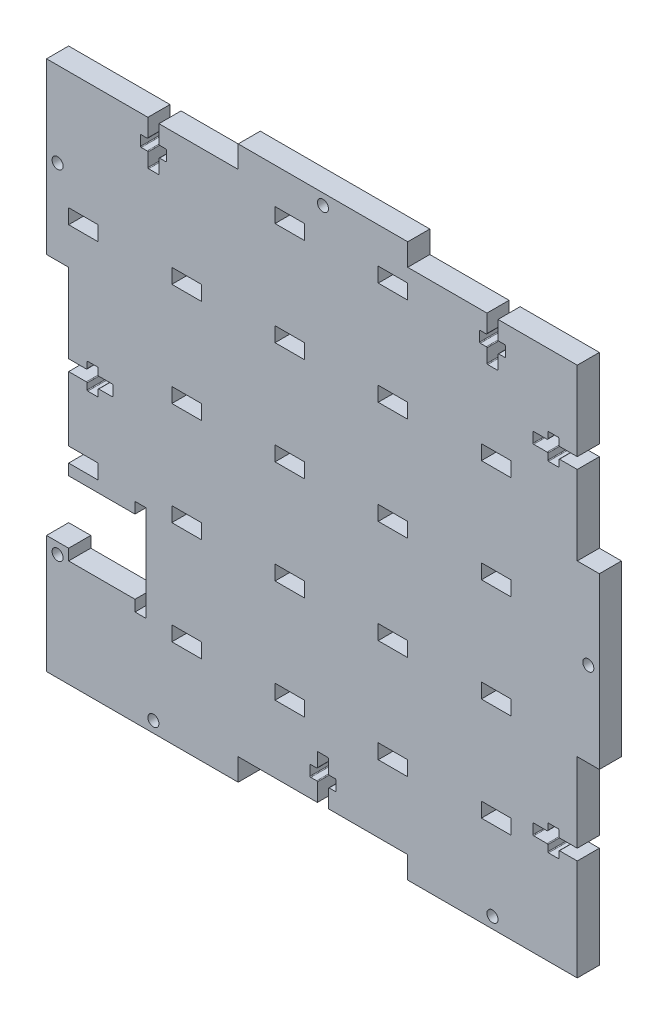
SolidWorks part; units mm, degrees
ref_plane "Front Plane" through (0, 0, 0) normal (0, 0, 1) x (1, 0, 0)
ref_plane "Top Plane" through (0, 0, 0) normal (0, 1, 0) x (1, 0, 0)
ref_plane "Right Plane" through (0, 0, 0) normal (1, 0, 0) x (0, 0, -1)
sketch "Sketch1" plane through (0, 0, 0) normal (0, 0, 1) x (1, 0, 0)
  line L0 (-69, 69) -> (-23, 69)
  line L5 (-75, -75) -> (75, -75) construction
  line L6 (-75, -75) -> (-75, 75) construction
  line L7 (-75, 75) -> (75, 75) construction
  line L8 (75, -75) -> (75, 75) construction
  line L9 (75, 23) -> (69, 23)
  line L10 (69, -23) -> (75, -23)
  line L11 (-69, -69) -> (69, -69) construction
  line L12 (-69, -69) -> (-69, 69) construction
  line L13 (-69, 69) -> (69, 69) construction
  line L14 (69, -69) -> (69, 69) construction
  line L15 (-69, -69) -> (69, 69) construction
  line L16 (69, -69) -> (69, -23)
  line L17 (-23, 69) -> (-23, 75)
  line L18 (-23, 75) -> (23, 75)
  line L19 (23, 75) -> (23, 69)
  line L20 (23, 69) -> (69, 69)
  line L21 (75, -23) -> (75, 23)
  line L22 (69, 23) -> (69, 69)
  line L23 (-75, 23) -> (-69, 23)
  line L24 (-69, 69) -> (-75, 69)
  line L25 (-75, 69) -> (-75, 23)
  line L26 (69, -69) -> (69, -75)
  line L27 (69, -75) -> (23, -75)
  line L28 (23, -75) -> (23, -69)
  line L29 (23, -69) -> (-23, -69)
  line L30 (-23, -69) -> (-23, -75)
  line L31 (-23, -75) -> (-69, -75)
  line L32 (-69, -75) -> (-69, -69) construction
  line L33 (-69, 23) -> (-69, -23)
  line L34 (-69, -23) -> (-75, -23)
  line L35 (-75, -23) -> (-75, -69)
  line L36 (-75, -69) -> (-69, -69) construction
  line L37 (-46, 69) -> (-46, -75) construction
  line L38 (-69, 69) -> (69, -69) construction
  line L39 (-75, -75) -> (-69, -75)
  line L40 (-75, -75) -> (-75, -69)
  point P0 (0, 0)
  point P6 (-7, -7)
  point P26 (0, -75)
  point P27 (-75, 0)
  dimension "D1" = 150
  dimension "D2" = 150
  dimension "D5" = 46
  dimension "D3" = 6
  dimension "D6" = 6
  dimension "D7" = 6
extrude "Box Side" add sketch "Sketch1" along normal blind 6
sketch "Sketch2" plane through (0, 0, 6) normal (0, 0, 1) x (1, 0, 0)
  line L0 (23, 72) -> (-23, 72) construction
  line L1 (23, 75) -> (23, 69) construction
  line L2 (-23, 69) -> (-23, 75) construction
  line L3 (-46, 69) -> (-46, -75) construction
  line L5 (0, 75) -> (0, 69) construction
  line L6 (-23, 75) -> (23, 75) construction
  line L7 (-69, 69) -> (69, 69) construction
  line L16 (-46, 69) -> (-46, -75) construction
  line L21 (0, -69) -> (0, 69) construction
  line L35 (-69, 69) -> (-23, 69) construction
  line L36 (-44.5, 69) -> (-44.5, 64.2)
  line L37 (-44.3, 64) -> (-42.7, 64)
  line L38 (-42.5, 63.8) -> (-42.5, 61.2)
  line L39 (-42.7, 61) -> (-44.3, 61)
  line L40 (-44.5, 60.8) -> (-44.5, 57.2)
  line L46 (-44.7, 57) -> (-47.3, 57)
  line L48 (-44.5, 69) -> (-47.5, 69)
  line L51 (-47.5, 60.8) -> (-47.5, 57.2)
  line L52 (-49.3, 61) -> (-47.7, 61)
  line L53 (-49.5, 63.8) -> (-49.5, 61.2)
  line L54 (-47.7, 64) -> (-49.3, 64)
  line L55 (-47.5, 69) -> (-47.5, 64.2)
  line L56 (47.5, 69) -> (47.5, 64.2)
  line L57 (47.7, 64) -> (49.3, 64)
  line L58 (49.5, 63.8) -> (49.5, 61.2)
  line L59 (49.3, 61) -> (47.7, 61)
  line L60 (47.5, 60.8) -> (47.5, 57.2)
  line L61 (44.5, 69) -> (47.5, 69)
  line L62 (44.7, 57) -> (47.3, 57)
  line L63 (44.5, 60.8) -> (44.5, 57.2)
  line L64 (42.7, 61) -> (44.3, 61)
  line L65 (42.5, 63.8) -> (42.5, 61.2)
  line L66 (44.3, 64) -> (42.7, 64)
  line L67 (44.5, 69) -> (44.5, 64.2)
  line L68 (-69, -69) -> (69, 69) construction
  line L69 (-69, -69) -> (69, 69) construction
  line L70 (75, 0) -> (69, 0) construction
  line L71 (72, 23) -> (72, -23) construction
  line L72 (69, 44.5) -> (64.2, 44.5)
  line L73 (64, 44.3) -> (64, 42.7)
  line L74 (63.8, 42.5) -> (61.2, 42.5)
  line L75 (61, 42.7) -> (61, 44.3)
  line L76 (60.8, 44.5) -> (57.2, 44.5)
  line L77 (57, 44.7) -> (57, 47.3)
  line L78 (69, 44.5) -> (69, 47.5)
  line L79 (60.8, 47.5) -> (57.2, 47.5)
  line L80 (61, 49.3) -> (61, 47.7)
  line L81 (63.8, 49.5) -> (61.2, 49.5)
  line L82 (64, 47.7) -> (64, 49.3)
  line L83 (69, 47.5) -> (64.2, 47.5)
  line L84 (69, -47.5) -> (64.2, -47.5)
  line L85 (64, -47.7) -> (64, -49.3)
  line L86 (63.8, -49.5) -> (61.2, -49.5)
  line L87 (61, -49.3) -> (61, -47.7)
  line L88 (60.8, -47.5) -> (57.2, -47.5)
  line L89 (69, -44.5) -> (69, -47.5)
  line L90 (57, -44.7) -> (57, -47.3)
  line L91 (60.8, -44.5) -> (57.2, -44.5)
  line L92 (61, -42.7) -> (61, -44.3)
  line L93 (63.8, -42.5) -> (61.2, -42.5)
  line L94 (64, -44.3) -> (64, -42.7)
  line L95 (69, -44.5) -> (64.2, -44.5)
  line L120 (-69, 69) -> (69, -69) construction
  line L121 (-69, 69) -> (69, -69) construction
  line L122 (-1.5, -69) -> (1.5, -69)
  line L123 (-23, -69) -> (23, -69) construction
  line L124 (1.5, -69) -> (1.5, -64.2)
  line L125 (1.7, -64) -> (3.3, -64)
  line L126 (3.5, -63.8) -> (3.5, -61.2)
  line L127 (3.3, -61) -> (1.7, -61)
  line L128 (1.5, -60.8) -> (1.5, -57.2)
  line L129 (1.3, -57) -> (-1.3, -57)
  line L130 (-1.5, -60.8) -> (-1.5, -57.2)
  line L131 (-3.3, -61) -> (-1.7, -61)
  line L132 (-3.5, -63.8) -> (-3.5, -61.2)
  line L133 (-1.7, -64) -> (-3.3, -64)
  line L134 (-1.5, -69) -> (-1.5, -64.2)
  line L135 (-69, -1.5) -> (-64.2, -1.5)
  line L136 (-64, -1.7) -> (-64, -3.3)
  line L137 (-63.8, -3.5) -> (-61.2, -3.5)
  line L138 (-61, -3.3) -> (-61, -1.7)
  line L139 (-60.8, -1.5) -> (-57.2, -1.5)
  line L140 (-57, 1.3) -> (-57, -1.3)
  line L141 (-60.8, 1.5) -> (-57.2, 1.5)
  line L142 (-61, 3.3) -> (-61, 1.7)
  line L143 (-63.8, 3.5) -> (-61.2, 3.5)
  line L144 (-64, 1.7) -> (-64, 3.3)
  line L145 (-69, 1.5) -> (-64.2, 1.5)
  line L146 (-69, -1.5) -> (-69, 1.5)
  line L147 (-69, -72) -> (-23, -72) construction
  line L148 (-23, 69) -> (-75, 69) construction
  line L149 (-23, -75) -> (-23, -69) construction
  line L150 (-69, -69) -> (-69, -75) construction
  line L151 (-75, -75) -> (-23, -75) construction
  circle A0 centre (0, 72) radius 1.5
  arc A1 (-44.5, 57.2) -> (-44.7, 57) centre (-44.7, 57.2) cw
  arc A2 (-44.3, 61) -> (-44.5, 60.8) centre (-44.3, 60.8) ccw
  arc A3 (-42.5, 61.2) -> (-42.7, 61) centre (-42.7, 61.2) cw
  arc A4 (-42.7, 64) -> (-42.5, 63.8) centre (-42.7, 63.8) cw
  arc A5 (-44.5, 64.2) -> (-44.3, 64) centre (-44.3, 64.2) ccw
  arc A6 (-47.5, 64.2) -> (-47.7, 64) centre (-47.7, 64.2) cw
  arc A7 (-49.3, 64) -> (-49.5, 63.8) centre (-49.3, 63.8) ccw
  arc A8 (-49.5, 61.2) -> (-49.3, 61) centre (-49.3, 61.2) ccw
  arc A9 (-47.7, 61) -> (-47.5, 60.8) centre (-47.7, 60.8) cw
  arc A10 (-47.5, 57.2) -> (-47.3, 57) centre (-47.3, 57.2) ccw
  arc A11 (47.5, 57.2) -> (47.3, 57) centre (47.3, 57.2) cw
  arc A12 (47.7, 61) -> (47.5, 60.8) centre (47.7, 60.8) ccw
  arc A13 (49.5, 61.2) -> (49.3, 61) centre (49.3, 61.2) cw
  arc A14 (49.3, 64) -> (49.5, 63.8) centre (49.3, 63.8) cw
  arc A15 (47.5, 64.2) -> (47.7, 64) centre (47.7, 64.2) ccw
  arc A16 (44.5, 64.2) -> (44.3, 64) centre (44.3, 64.2) cw
  arc A17 (42.7, 64) -> (42.5, 63.8) centre (42.7, 63.8) ccw
  arc A18 (42.5, 61.2) -> (42.7, 61) centre (42.7, 61.2) ccw
  arc A19 (44.3, 61) -> (44.5, 60.8) centre (44.3, 60.8) cw
  arc A20 (44.5, 57.2) -> (44.7, 57) centre (44.7, 57.2) ccw
  arc A21 (57.2, 44.5) -> (57, 44.7) centre (57.2, 44.7) cw
  arc A22 (61, 44.3) -> (60.8, 44.5) centre (60.8, 44.3) ccw
  arc A23 (61.2, 42.5) -> (61, 42.7) centre (61.2, 42.7) cw
  arc A24 (64, 42.7) -> (63.8, 42.5) centre (63.8, 42.7) cw
  arc A25 (64.2, 44.5) -> (64, 44.3) centre (64.2, 44.3) ccw
  arc A26 (64.2, 47.5) -> (64, 47.7) centre (64.2, 47.7) cw
  arc A27 (64, 49.3) -> (63.8, 49.5) centre (63.8, 49.3) ccw
  arc A28 (61.2, 49.5) -> (61, 49.3) centre (61.2, 49.3) ccw
  arc A29 (61, 47.7) -> (60.8, 47.5) centre (60.8, 47.7) cw
  arc A30 (57.2, 47.5) -> (57, 47.3) centre (57.2, 47.3) ccw
  arc A31 (57.2, -47.5) -> (57, -47.3) centre (57.2, -47.3) cw
  arc A32 (61, -47.7) -> (60.8, -47.5) centre (60.8, -47.7) ccw
  arc A33 (61.2, -49.5) -> (61, -49.3) centre (61.2, -49.3) cw
  arc A34 (64, -49.3) -> (63.8, -49.5) centre (63.8, -49.3) cw
  arc A35 (64.2, -47.5) -> (64, -47.7) centre (64.2, -47.7) ccw
  arc A36 (64.2, -44.5) -> (64, -44.3) centre (64.2, -44.3) cw
  arc A37 (64, -42.7) -> (63.8, -42.5) centre (63.8, -42.7) ccw
  arc A38 (61.2, -42.5) -> (61, -42.7) centre (61.2, -42.7) ccw
  arc A39 (61, -44.3) -> (60.8, -44.5) centre (60.8, -44.3) cw
  arc A40 (57.2, -44.5) -> (57, -44.7) centre (57.2, -44.7) ccw
  circle A41 centre (72, 0) radius 1.5
  arc A62 (1.5, -57.2) -> (1.3, -57) centre (1.3, -57.2) ccw
  arc A63 (1.7, -61) -> (1.5, -60.8) centre (1.7, -60.8) cw
  arc A64 (3.5, -61.2) -> (3.3, -61) centre (3.3, -61.2) ccw
  arc A65 (3.3, -64) -> (3.5, -63.8) centre (3.3, -63.8) ccw
  arc A66 (1.5, -64.2) -> (1.7, -64) centre (1.7, -64.2) cw
  arc A67 (-1.5, -64.2) -> (-1.7, -64) centre (-1.7, -64.2) ccw
  arc A68 (-3.3, -64) -> (-3.5, -63.8) centre (-3.3, -63.8) cw
  arc A69 (-3.5, -61.2) -> (-3.3, -61) centre (-3.3, -61.2) cw
  arc A70 (-1.7, -61) -> (-1.5, -60.8) centre (-1.7, -60.8) ccw
  arc A71 (-1.5, -57.2) -> (-1.3, -57) centre (-1.3, -57.2) cw
  arc A72 (-57.2, -1.5) -> (-57, -1.3) centre (-57.2, -1.3) ccw
  arc A73 (-61, -1.7) -> (-60.8, -1.5) centre (-60.8, -1.7) cw
  arc A74 (-61.2, -3.5) -> (-61, -3.3) centre (-61.2, -3.3) ccw
  arc A75 (-64, -3.3) -> (-63.8, -3.5) centre (-63.8, -3.3) ccw
  arc A76 (-64.2, -1.5) -> (-64, -1.7) centre (-64.2, -1.7) cw
  arc A77 (-64.2, 1.5) -> (-64, 1.7) centre (-64.2, 1.7) ccw
  arc A78 (-64, 3.3) -> (-63.8, 3.5) centre (-63.8, 3.3) cw
  arc A79 (-61.2, 3.5) -> (-61, 3.3) centre (-61.2, 3.3) cw
  arc A80 (-61, 1.7) -> (-60.8, 1.5) centre (-60.8, 1.7) ccw
  arc A81 (-57.2, 1.5) -> (-57, 1.3) centre (-57.2, 1.3) cw
  circle A82 centre (-46, -72) radius 1.5
  circle A83 centre (46, -72) radius 1.5
  circle A84 centre (-72, 46) radius 1.5
  circle A85 centre (-72, -46) radius 1.5
  point P6 (0, 72)
  point P38 (0, 0)
  point P56 (-46, 57)
  point P88 (46, 57)
  point P161 (57, 46)
  point P162 (57, -46)
  point P198 (0, -57)
  point P231 (-57, 0)
  point P234 (-42.5, 62.5)
  dimension "D1" = 3
  dimension "D2" = 0.2
  dimension "D8" = 0.2
  dimension "D14" = 3
  dimension "D4" = 3
  dimension "D7" = 1.5
  dimension "D10" = 3
  dimension "D12" = 1.5
  dimension "D9" = 12
  dimension "D11" = 5
  dimension "D13" = 7
  dimension "D3" = 12
  dimension "D5" = 7
  dimension "D6" = 5
extrude "Screw Cut-outs" cut sketch "Sketch2" against normal through all
sketch "Sketch3" plane through (0, 0, 6) normal (0, 0, 1) x (1, 0, 0)
  line L0 (-75, -75) -> (-23, -75) construction
  line L1 (-75, -49) -> (-48, -49)
  line L2 (-75, -49) -> (-75, -23)
  line L3 (-75, -23) -> (-48, -23)
  line L4 (-48, -49) -> (-48, -23)
  line L5 (-75, -23) -> (-75, -75) construction
  line L6 (-75, -46) -> (-48, -46)
  line L7 (-75, -26) -> (-48, -26)
  line L9 (-75, -26) -> (-69, -26)
  line L10 (-75, -26) -> (-75, -29)
  line L11 (-75, -29) -> (-69, -29)
  line L12 (-69, -26) -> (-69, -29)
  line L13 (-75, -46) -> (-69, -46)
  line L14 (-75, -46) -> (-75, -43)
  line L15 (-75, -43) -> (-69, -43)
  line L16 (-69, -46) -> (-69, -43)
  line L17 (-69, -26) -> (-75, -26)
  line L18 (-69, -26) -> (-69, -23)
  line L19 (-69, -23) -> (-75, -23)
  line L20 (-75, -26) -> (-75, -23)
  line L25 (-48, -23) -> (-51, -23)
  line L26 (-48, -23) -> (-48, -26)
  line L27 (-48, -26) -> (-51, -26)
  line L28 (-51, -23) -> (-51, -26)
  line L29 (-48, -46) -> (-51, -46)
  line L30 (-48, -46) -> (-48, -49)
  line L31 (-48, -49) -> (-51, -49)
  line L32 (-51, -46) -> (-51, -49)
  dimension "D1" = 26
  dimension "D2" = 27
  dimension "D3" = 26
  dimension "D4" = 20
  dimension "D5" = 3
  dimension "D6" = 3
  dimension "D7" = 6
  dimension "D8" = 3
  dimension "D9" = 3
extrude "Cut-Extrude1" cut sketch "Sketch3" against normal through all contours L7 L2 L6 L4 | L10 L9 L12 L11 | L18 L17 L20 L19 | L26 L25 L28 L27 | L30 L29 L32 L31 region at (-60.75, -36, 6)
sketch "Sketch4" plane through (0, 0, 6) normal (0, 0, 1) x (1, 0, 0)
  line L0 (-33, 65) -> (-33, 61) construction
  line L1 (-69, 65) -> (-61, 65) construction
  line L2 (-69, 65) -> (-69, 61) construction
  line L3 (-69, 61) -> (-61, 61) construction
  line L4 (-61, 65) -> (-61, 61) construction
  line L5 (-65, 63) -> (-37, 63) construction
  line L6 (-65, 63) -> (-65, 35) construction
  line L7 (-65, 35) -> (-37, 35) construction
  line L8 (-37, 63) -> (-37, 35) construction
  line L9 (-65, 63) -> (-37, 35) construction
  line L10 (-65, 35) -> (-37, 63) construction
  line L11 (-41, 65) -> (-33, 65) construction
  line L12 (-41, 65) -> (-41, 61) construction
  line L13 (-41, 61) -> (-33, 61) construction
  line L14 (-33, 37) -> (-33, 33)
  line L15 (-41, 37) -> (-33, 37)
  line L16 (-41, 37) -> (-41, 33)
  line L17 (-41, 33) -> (-33, 33)
  line L18 (-61, 37) -> (-61, 33)
  line L19 (-69, 37) -> (-61, 37)
  line L20 (-69, 37) -> (-69, 33)
  line L21 (-69, 33) -> (-61, 33)
  line L22 (-47.5, 69) -> (-75, 69) construction
  line L23 (-75, 69) -> (-75, 23) construction
  line L24 (15, 33.2836) -> (23, 33.2836)
  line L25 (15, 37.2836) -> (23, 37.2836)
  line L26 (15, 37.2836) -> (15, 33.2836)
  line L27 (23, 37.2836) -> (23, 33.2836)
  line L28 (-5, 37.2836) -> (-5, 33.2836)
  line L29 (-13, 33.2836) -> (-5, 33.2836)
  line L30 (-13, 37.2836) -> (-13, 33.2836)
  line L31 (-13, 37.2836) -> (-5, 37.2836)
  line L32 (-13, 61.2836) -> (-5, 61.2836)
  line L33 (-13, 65.2836) -> (-13, 61.2836)
  line L34 (-13, 65.2836) -> (-5, 65.2836)
  line L35 (-5, 65.2836) -> (-5, 61.2836)
  line L36 (23, 65.2836) -> (23, 61.2836)
  line L37 (15, 61.2836) -> (23, 61.2836)
  line L38 (15, 65.2836) -> (23, 65.2836)
  line L39 (15, 65.2836) -> (15, 61.2836)
  line L44 (51, 37.5671) -> (51, 33.5671)
  line L45 (43, 33.5671) -> (51, 33.5671)
  line L46 (43, 37.5671) -> (43, 33.5671)
  line L47 (43, 37.5671) -> (51, 37.5671)
  line L48 (43, 61.5671) -> (51, 61.5671) construction
  line L49 (43, 65.5671) -> (43, 61.5671) construction
  line L50 (43, 65.5671) -> (51, 65.5671) construction
  line L51 (51, 65.5671) -> (51, 61.5671) construction
  line L56 (15, -22.7164) -> (23, -22.7164)
  line L57 (15, -18.7164) -> (23, -18.7164)
  line L58 (15, -18.7164) -> (15, -22.7164)
  line L59 (23, -18.7164) -> (23, -22.7164)
  line L60 (-5, -18.7164) -> (-5, -22.7164)
  line L61 (-13, -22.7164) -> (-5, -22.7164)
  line L62 (-13, -18.7164) -> (-13, -22.7164)
  line L63 (-13, -18.7164) -> (-5, -18.7164)
  line L64 (-13, 5.2836) -> (-5, 5.2836)
  line L65 (-13, 9.2836) -> (-13, 5.2836)
  line L66 (-13, 9.2836) -> (-5, 9.2836)
  line L67 (-5, 9.2836) -> (-5, 5.2836)
  line L68 (23, 9.2836) -> (23, 5.2836)
  line L69 (15, 5.2836) -> (23, 5.2836)
  line L70 (15, 9.2836) -> (23, 9.2836)
  line L71 (15, 9.2836) -> (15, 5.2836)
  line L76 (51, -18.4329) -> (51, -22.4329)
  line L77 (43, -22.4329) -> (51, -22.4329)
  line L78 (43, -18.4329) -> (43, -22.4329)
  line L79 (43, -18.4329) -> (51, -18.4329)
  line L80 (43, 5.5671) -> (51, 5.5671)
  line L81 (43, 9.5671) -> (43, 5.5671)
  line L82 (43, 9.5671) -> (51, 9.5671)
  line L83 (51, 9.5671) -> (51, 5.5671)
  line L96 (-13, -50.7164) -> (-5, -50.7164)
  line L97 (-13, -46.7164) -> (-13, -50.7164)
  line L98 (-13, -46.7164) -> (-5, -46.7164)
  line L99 (-5, -46.7164) -> (-5, -50.7164)
  line L100 (23, -46.7164) -> (23, -50.7164)
  line L101 (15, -50.7164) -> (23, -50.7164)
  line L102 (15, -46.7164) -> (23, -46.7164)
  line L103 (15, -46.7164) -> (15, -50.7164)
  line L112 (43, -50.4329) -> (51, -50.4329)
  line L113 (43, -46.4329) -> (43, -50.4329)
  line L114 (43, -46.4329) -> (51, -46.4329)
  line L115 (51, -46.4329) -> (51, -50.4329)
  line L120 (-41, -23) -> (-33, -23)
  line L121 (-41, -19) -> (-33, -19)
  line L122 (-41, -19) -> (-41, -23)
  line L123 (-33, -19) -> (-33, -23)
  line L124 (-61, -19) -> (-61, -23)
  line L125 (-69, -23) -> (-61, -23)
  line L126 (-69, -19) -> (-69, -23)
  line L127 (-69, -19) -> (-61, -19)
  line L128 (-69, 5) -> (-61, 5) construction
  line L129 (-69, 9) -> (-69, 5) construction
  line L130 (-69, 9) -> (-61, 9) construction
  line L131 (-61, 9) -> (-61, 5) construction
  line L132 (-33, 9) -> (-33, 5)
  line L133 (-41, 5) -> (-33, 5)
  line L134 (-41, 9) -> (-33, 9)
  line L135 (-41, 9) -> (-41, 5)
  line L144 (-69, -51) -> (-61, -51) construction
  line L145 (-69, -47) -> (-69, -51) construction
  line L146 (-69, -47) -> (-61, -47) construction
  line L147 (-61, -47) -> (-61, -51) construction
  line L148 (-33, -47) -> (-33, -51)
  line L149 (-41, -51) -> (-33, -51)
  line L150 (-41, -47) -> (-33, -47)
  line L151 (-41, -47) -> (-41, -51)
  line L152 (15, -78.7164) -> (23, -78.7164) [skipped]
  line L153 (15, -74.7164) -> (23, -74.7164) [skipped]
  line L154 (15, -74.7164) -> (15, -78.7164) [skipped]
  line L155 (23, -74.7164) -> (23, -78.7164) [skipped]
  line L156 (-5, -74.7164) -> (-5, -78.7164) [skipped]
  line L157 (-13, -78.7164) -> (-5, -78.7164) [skipped]
  line L158 (-13, -74.7164) -> (-13, -78.7164) [skipped]
  line L159 (-13, -74.7164) -> (-5, -74.7164) [skipped]
  line L160 (71, -78.4329) -> (79, -78.4329) [skipped]
  line L161 (71, -74.4329) -> (79, -74.4329) [skipped]
  line L162 (71, -74.4329) -> (71, -78.4329) [skipped]
  line L163 (79, -74.4329) -> (79, -78.4329) [skipped]
  line L164 (51, -74.4329) -> (51, -78.4329) [skipped]
  line L165 (43, -78.4329) -> (51, -78.4329) [skipped]
  line L166 (43, -74.4329) -> (43, -78.4329) [skipped]
  line L167 (43, -74.4329) -> (51, -74.4329) [skipped]
  line L168 (-41, -79) -> (-33, -79) [skipped]
  line L169 (-41, -75) -> (-33, -75) [skipped]
  line L170 (-41, -75) -> (-41, -79) [skipped]
  line L171 (-33, -75) -> (-33, -79) [skipped]
  line L172 (-61, -75) -> (-61, -79) [skipped]
  line L173 (-69, -79) -> (-61, -79) [skipped]
  line L174 (-69, -75) -> (-69, -79) [skipped]
  line L175 (-69, -75) -> (-61, -75) [skipped]
  line L176 (71, 33.5671) -> (79, 33.5671) [skipped]
  line L177 (71, 37.5671) -> (79, 37.5671) [skipped]
  line L178 (71, 37.5671) -> (71, 33.5671) [skipped]
  line L179 (79, 37.5671) -> (79, 33.5671) [skipped]
  line L180 (79, 65.5671) -> (79, 61.5671) [skipped]
  line L181 (71, 61.5671) -> (79, 61.5671) [skipped]
  line L182 (71, 65.5671) -> (79, 65.5671) [skipped]
  line L183 (71, 65.5671) -> (71, 61.5671) [skipped]
  line L184 (71, -22.4329) -> (79, -22.4329) [skipped]
  line L185 (71, -18.4329) -> (79, -18.4329) [skipped]
  line L186 (71, -18.4329) -> (71, -22.4329) [skipped]
  line L187 (79, -18.4329) -> (79, -22.4329) [skipped]
  line L188 (79, 9.5671) -> (79, 5.5671) [skipped]
  line L189 (71, 5.5671) -> (79, 5.5671) [skipped]
  line L190 (71, 9.5671) -> (79, 9.5671) [skipped]
  line L191 (71, 9.5671) -> (71, 5.5671) [skipped]
  line L192 (79, -46.4329) -> (79, -50.4329) [skipped]
  line L193 (71, -50.4329) -> (79, -50.4329) [skipped]
  line L194 (71, -46.4329) -> (79, -46.4329) [skipped]
  line L195 (71, -46.4329) -> (71, -50.4329) [skipped]
  circle A0 centre (-65, 63) radius 2 construction
  point P6 (-65, 61)
  point P7 (-69, 35)
  point P8 (-65, 33)
  point P12 (-51, 49)
  point P13 (-37, 33)
  point P33 (-37, 61)
  point P41 (-65, 37)
  dimension "D1" = 8
  dimension "D2" = 4
  dimension "D3" = 2
  dimension "D5" = 28
  dimension "D6" = 6
  dimension "D7" = 10
  dimension "D10" = 20
  dimension "D11" = 24
  dimension "D4" = 2
  dimension "D8" = 3
  dimension "D9" = 3
extrude "Cut-Extrude2" cut sketch "Sketch4" against normal through all
equation "\"filletRadius\"=0.2"
equation "\"D8@Sketch2\"=\"filletRadius\""
equation "\"D2@Sketch2\"=\"filletRadius\""
equation "\"fingerWidth\"= 46"
equation "\"D5@Sketch1\"=\"fingerWidth\""
equation "\"wallThickness\"= 6"
equation "\"D3@Sketch1\" = \"wallThickness\""
equation "\"D6@Sketch1\" = \"wallThickness\""
equation "\"D7@Sketch1\" = \"wallThickness\""
equation "\"D1@Box Side\" = \"wallThickness\""
equation "\"M3\"= 3"
equation "\"D14@Sketch2\"=\"M3\""
equation "\"D1@Sketch2\"=\"M3\""
equation "\"D12@Sketch2\"=\"M3\"/2"
equation "\"nutThickness\"=3"
equation "\"D10@Sketch2\" = \"nutThickness\""
equation "\"boltLength\"= 12"
equation "\"D9@Sketch2\" = \"boltLength\""
equation "\"distanceToNut\"= 5"
equation "\"D11@Sketch2\" = \"distanceToNut\""
equation "\"D13@Sketch2\" = \"nutWidth\""
equation "\"D7@Sketch2\"=\"M3\"/2"
equation "\"D4@Sketch2\" = \"nutThickness\""
equation "\"D3@Sketch2\" = \"boltLength\""
equation "\"D5@Sketch2\" = \"nutWidth\""
equation "\"D6@Sketch2\" = \"distanceToNut\""
equation "\"sideLength\"=150"
equation "\"D1@Sketch1\"=\"sideLength\""
equation "\"D2@Sketch1\"=\"sideLength\""
equation "\"nutWidth\"=7"
